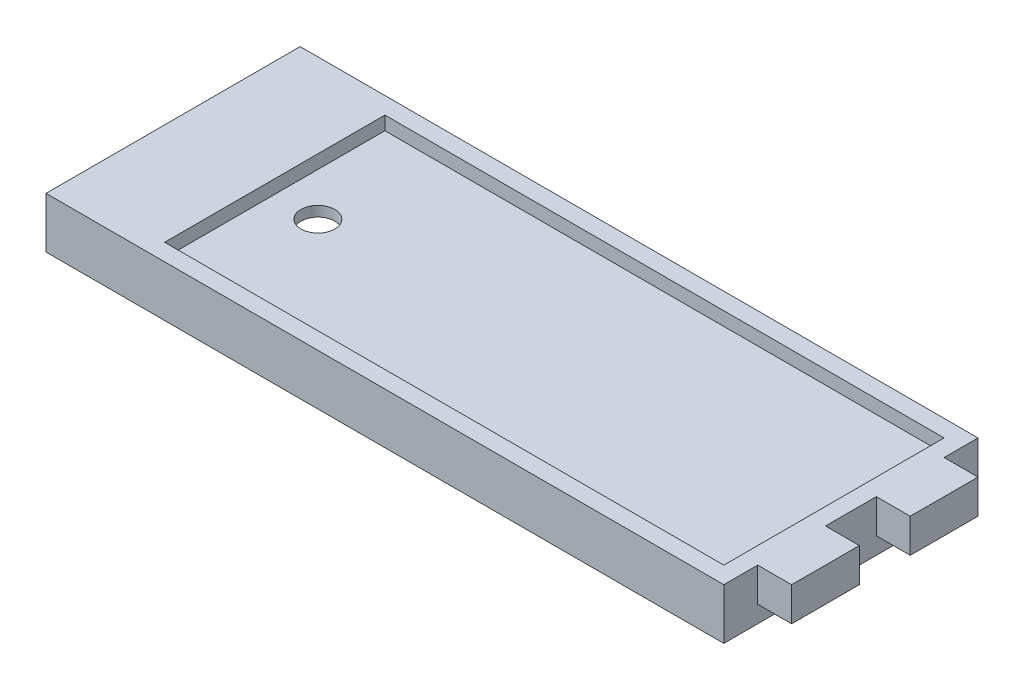
SolidWorks part; units mm, degrees
ref_plane "Front Plane" through (0, 0, 0) normal (0, 0, 1) x (1, 0, 0)
ref_plane "Top Plane" through (0, 0, 0) normal (0, 1, 0) x (1, 0, 0)
ref_plane "Right Plane" through (0, 0, 0) normal (1, 0, 0) x (0, 0, -1)
sketch "Sketch1" plane through (0, 0, 0) normal (0, 1, 0) x (1, 0, 0)
  line L1 (-60, 37.5) -> (140, 37.5)
  line L2 (-60, 37.5) -> (-60, -37.5)
  line L3 (-60, -37.5) -> (140, -37.5)
  line L4 (140, 37.5) -> (140, -37.5)
  point P0 (0, 0)
  dimension "D1" = 200
  dimension "D2" = 75
extrude "Boss-Extrude1" add sketch "Sketch1" along normal blind 15
sketch "Sketch9" plane through (0, 15, 0) normal (0, 1, 0) x (1, 0, 0)
  line L1 (-30, 32.5) -> (135, 32.5)
  line L2 (-30, 32.5) -> (-30, -32.5)
  line L3 (-30, -32.5) -> (135, -32.5)
  line L4 (135, 32.5) -> (135, -32.5)
  line L5 (140, -37.5) -> (140, 37.5) construction
  point P4 (135, 0)
  dimension "D1" = 165
  dimension "D2" = 65
  dimension "D3" = 0
  dimension "D4" = 5
extrude "Cut-Extrude5" cut sketch "Sketch9" against normal blind 4
shell "Shell3" thickness 3 removed face at (40, 0, 0) removed face at (-60, 7.5, 0)
sketch "Sketch14" plane through (140, 0, 0) normal (1, 0, 0) x (0, 0, -1)
  line L1 (-27.5, 15) -> (-7.5, 15)
  line L2 (-27.5, 15) -> (-27.5, 5)
  line L3 (-27.5, 5) -> (-7.5, 5)
  line L4 (-7.5, 15) -> (-7.5, 5)
  line L5 (7.5, 15) -> (27.5, 15)
  line L6 (7.5, 15) -> (7.5, 5)
  line L7 (7.5, 5) -> (27.5, 5)
  line L8 (27.5, 15) -> (27.5, 5)
  line L9 (-37.5, 15) -> (37.5, 15) construction
  line L10 (-37.5, 15) -> (-37.5, 0) construction
  line L11 (37.5, 15) -> (37.5, 0) construction
  point P12 (-37.5, 7.5)
  dimension "D1" = 20
  dimension "D2" = 10
  dimension "D3" = 10
  dimension "D4" = 10
extrude "Boss-Extrude5" add sketch "Sketch14" along normal blind 10
sketch "Sketch15" plane through (0, 11, 0) normal (0, 1, 0) x (1, 0, 0)
  circle A0 centre (-17.2823, 0) radius 5
extrude "Cut-Extrude7" cut sketch "Sketch15" against normal through all
